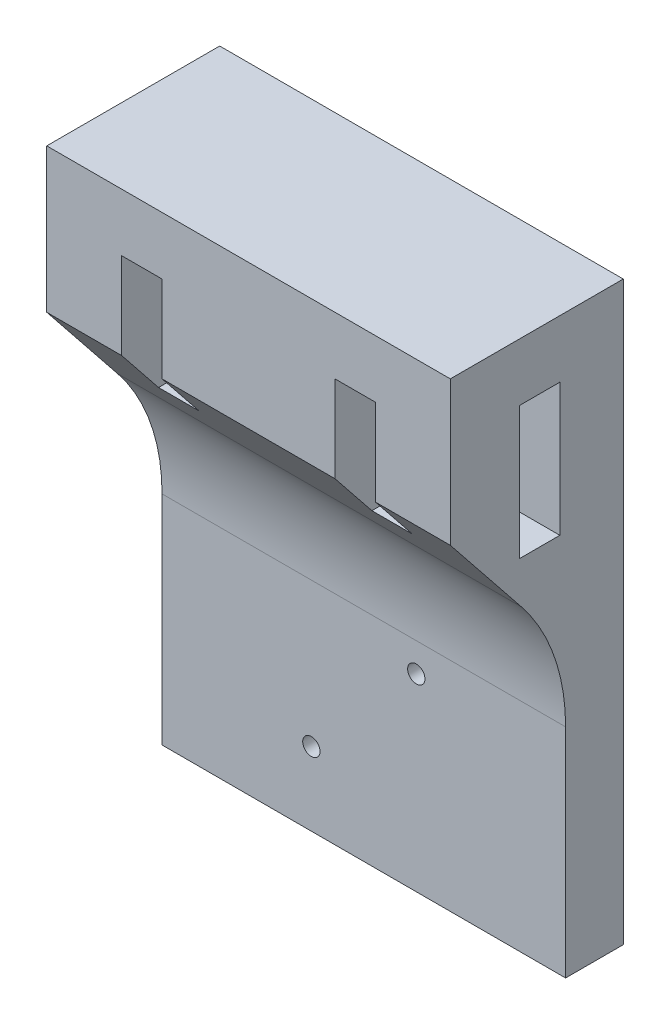
SolidWorks part; units mm, degrees
ref_plane "Front Plane" through (0, 0, 0) normal (0, 0, 1) x (1, 0, 0)
ref_plane "Top Plane" through (0, 0, 0) normal (0, 1, 0) x (1, 0, 0)
ref_plane "Right Plane" through (0, 0, 0) normal (1, 0, 0) x (0, 0, -1)
sketch "Sketch1" plane through (0, 0, 0) normal (0, 0, 1) x (1, 0, 0)
  line L1 (0, 0) -> (70, 0)
  line L2 (0, 0) -> (0, 100)
  line L3 (0, 100) -> (70, 100)
  line L4 (70, 0) -> (70, 100)
  dimension "D1" = 100
  dimension "D2" = 70
extrude "Boss-Extrude1" add sketch "Sketch1" along normal blind 30
sketch "Sketch2" plane through (0, 0, 0) normal (-1, 0, 0) x (0, 0, 1)
  line L0 (30, 100) -> (0, 100) construction
  line L1 (11, 90) -> (18, 90)
  line L2 (11, 90) -> (11, 67)
  line L3 (11, 67) -> (18, 67)
  line L4 (18, 90) -> (18, 67)
  line L9 (30, 100) -> (30, 0) construction
  dimension "D1" = 10
  dimension "D2" = 12
  dimension "D3" = 7
  dimension "D4" = 23
extrude "Cut-Extrude1" cut sketch "Sketch2" against normal blind 20
sketch "Sketch3" plane through (0, 0, 30) normal (0, 0, 1) x (1, 0, 0)
  line L0 (0, 100) -> (0, 0) construction
  line L1 (13, 90) -> (20, 90)
  line L2 (13, 90) -> (13, 67)
  line L3 (13, 67) -> (20, 67)
  line L4 (20, 90) -> (20, 67)
  line L5 (70, 100) -> (0, 100) construction
  dimension "D1" = 20
  dimension "D2" = 7
  dimension "D3" = 10
  dimension "D4" = 23
extrude "Cut-Extrude2" cut sketch "Sketch3" against normal blind 16
ref_plane "Plane1" through (35, 0, 0) normal (-1, 0, 0) x (0, 0, 1)
mirror "Mirror1" about plane through (35, 0, 0) normal (-1, 0, 0) of "Cut-Extrude2", "Cut-Extrude1"
sketch "Sketch4" plane through (0, 0, 0) normal (-1, 0, 0) x (0, 0, 1)
  line L0 (0, 100) -> (0, 0) construction
  line L1 (0, 50) -> (10, 50)
  line L2 (0, 50) -> (0, 0)
  line L3 (0, 0) -> (10, 0)
  line L4 (10, 37.7227) -> (10, 0)
  line L5 (30, 0) -> (0, 0) construction
  line L6 (30, 75) -> (17.6696, 59.587)
  line L7 (30, 100) -> (30, 0) construction
  line L8 (30, 0) -> (0, 0)
  line L9 (30, 100) -> (30, 0)
  arc A0 (17.6696, 59.587) -> (10, 37.7227) centre (45, 37.7227) ccw
  line M11 (0, 0) -> (30, 0)
  line M12 (30, 0) -> (30, 100)
  dimension "D3" = 35
  dimension "D1" = 10
  dimension "D2" = 50
  dimension "D4" = 75
extrude "Cut-Extrude3" cut sketch "Sketch4" against normal through all contours L6 A0 L4 M11 M12 region at (0, 31.4298, 20.7879)
sketch "Sketch5" plane through (0, 0, 10) normal (0, 0, 1) x (1, 0, 0)
  line L0 (0, 37.7227) -> (70, 37.7227) construction
  line L1 (35, 37.7227) -> (35, -15.2448) construction
  line L2 (35, 16.5) -> (35, -16.5) construction
  line L3 (25.9, 12.7227) -> (44.1, 12.7227)
  line L4 (44.1, 32.7227) -> (44.1, 12.7227)
  circle A0 centre (44.1, 32.7227) radius 1.5
  circle A1 centre (25.9, 12.7227) radius 1.5
  point P12 (35, 12.7227)
  dimension "D4" = 3
  dimension "D5" = 3
  dimension "D1" = 5
  dimension "D2" = 20
  dimension "D3" = 18.2
extrude "Cut-Extrude4" cut sketch "Sketch5" against normal blind 10 contours A0 | A1 region at (43.0693, 33.7533, 10) region at (24.4424, 12.7227, 10)
